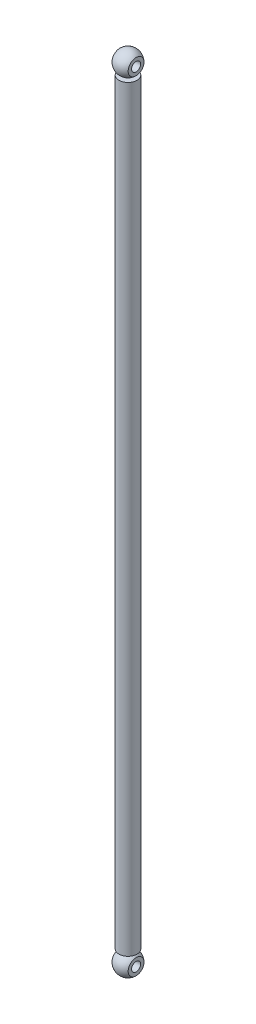
SolidWorks part; units mm, degrees
note: The reader was unsure of these and kept them because the rebuilt part matched: shared geometry of "草圖3<3>".
ref_plane "前基準面" through (0, 0, 0) normal (0, 0, 1) x (1, 0, 0)
ref_plane "上基準面" through (0, 0, 0) normal (0, 1, 0) x (1, 0, 0)
ref_plane "右基準面" through (0, 0, 0) normal (1, 0, 0) x (0, 0, -1)
sketch "草圖1" plane through (0, 0, 0) normal (0, 0, 1) x (1, 0, 0)
  line L0 (0, 0) -> (0, 449.671) construction
  line L1 (0, 0) -> (4, 0)
  line L2 (4, 0) -> (4, 334)
  line L3 (4, 334) -> (0, 334)
  line L4 (0, 0) -> (0, 334)
  dimension "D1" = 334
  dimension "D2" = 8
revolve "旋轉1" add sketch "草圖1" angle 360 about L0
sketch "草圖2" plane through (0, 0, 0) normal (0, 0, 1) x (1, 0, 0)
  line L0 (0, 347.5895) -> (0, -19.2885) construction
  line L1 (0, 0) -> (0, -10)
  line L2 (0, 334) -> (0, 344)
  line L3 (4, 334) -> (-4, 334) construction
  arc A0 (0, -10) -> (0, 0) centre (0, -5) ccw
  arc A1 (0, 344) -> (0, 334) centre (0, 339) cw
  dimension "D1" = 5
  dimension "D2" = 5
revolve "旋轉2" add sketch "草圖2" angle 360 about L0
sketch "草圖3" plane through (0, 0, 0) normal (0, 0, 1) x (1, 0, 0)
  line L0 (0, 334) -> (0, 345.5625) construction
  line L1 (4, 334) -> (-4, 334) construction
  line L2 (-8.7121, 334) -> (-8.7121, 347.0066)
  line L3 (3.5743, 334) -> (8.7121, 334)
  line L4 (3.5743, 334) -> (3.5743, 347.0066)
  line L5 (3.5743, 347.0066) -> (8.7121, 347.0066)
  line L6 (8.7121, 334) -> (8.7121, 347.0066)
  line L7 (-3.5743, 347.0066) -> (-8.7121, 347.0066)
  line L8 (-3.5743, 334) -> (-3.5743, 347.0066)
  line L9 (-3.5743, 334) -> (-8.7121, 334)
  line L10 (-4, 167) -> (42.4334, 167) construction
  line L11 (-4, 334) -> (-4, 0) construction
  line L12 (0, 0) -> (0, -11.5625) construction
  line L13 (-3.5743, 0) -> (-8.7121, 0)
  line L14 (-3.5743, 0) -> (-3.5743, -13.0066)
  line L15 (-3.5743, -13.0066) -> (-8.7121, -13.0066)
  line L16 (8.7121, 0) -> (8.7121, -13.0066)
  line L17 (3.5743, -13.0066) -> (8.7121, -13.0066)
  line L18 (3.5743, 0) -> (3.5743, -13.0066)
  line L19 (3.5743, 0) -> (8.7121, 0)
  line L20 (-8.7121, 0) -> (-8.7121, -13.0066)
extrude "除料-伸長1" cut sketch "草圖3" against normal mid plane 10
extrude "除料-伸長3" cut sketch "草圖3<3>" against normal mid plane 10
sketch "草圖3<3>" plane through (0, 0, 0) normal (0, 0, 1) x (1, 0, 0) same geometry as "草圖3"
sketch "草圖4" plane through (3.5743, 0, 0) normal (1, 0, 0) x (0, 0, -1)
  circle A0 centre (0, 339) radius 2
  circle A1 centre (0, -5) radius 2
  dimension "D1" = 4
  dimension "D2" = 4
extrude "除料-伸長4" cut sketch "草圖4" against normal blind 10
